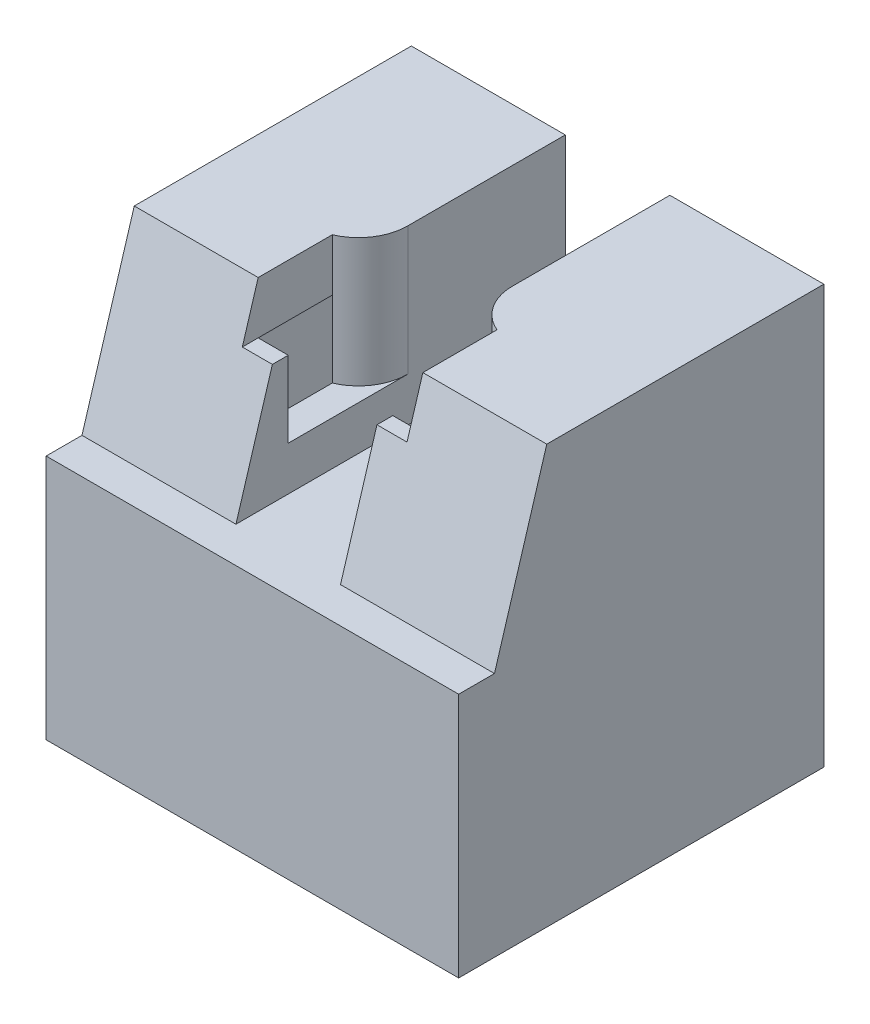
SolidWorks part; units mm, degrees
ref_plane "Front Plane" through (0, 0, 0) normal (0, 0, 1) x (1, 0, 0)
ref_plane "Top Plane" through (0, 0, 0) normal (0, 1, 0) x (1, 0, 0)
ref_plane "Right Plane" through (0, 0, 0) normal (1, 0, 0) x (0, 0, -1)
sketch "Sketch2" plane through (0, 0, 0) normal (0, 1, 0) x (1, 0, 0)
  line L1 (-9.35, 10) -> (9.35, 10)
  line L2 (-9.35, 10) -> (-9.35, -10)
  line L3 (-9.35, -10) -> (9.35, -10)
  line L4 (9.35, 10) -> (9.35, -10)
  point P4 (0, 10)
  point P6 (-9.35, 0)
  dimension "D1" = 18.7
  dimension "D2" = 20
extrude "Boss-Extrude1" add sketch "Sketch2" along normal blind 25.4
sketch "Sketch3" plane through (0, 0, -10) normal (0, 0, -1) x (-1, 0, 0)
  line L0 (-9.35, 25.4) -> (9.35, 25.4) construction
  line L1 (-3.175, 25.4) -> (3.175, 25.4)
  line L2 (-3.175, 25.4) -> (-3.175, 18.1)
  line L3 (-3.175, 18.1) -> (3.175, 18.1)
  line L4 (3.175, 25.4) -> (3.175, 18.1)
  line L5 (-9.35, 22.225) -> (9.35, 22.225) construction
  line L6 (-9.35, 25.4) -> (-9.35, 0) construction
  line L7 (9.35, 25.4) -> (9.35, 0) construction
  line L9 (-3.175, 18.1) -> (3.175, 18.1)
  line L10 (-3.175, 18.1) -> (-3.175, 14.925)
  line L11 (-3.175, 14.925) -> (3.175, 14.925)
  line L12 (3.175, 18.1) -> (3.175, 14.925)
  point P6 (0, 18.1)
  point P9 (6.0716, 19.725)
  line M12 (9.35, 25.4) -> (-9.35, 25.4)
  dimension "D1" = 6.35
  dimension "D2" = 3.175
  dimension "D3" = 2.5
  dimension "D4" = 1.625
  dimension "D5" = 3.175
extrude "Cut-Extrude1" cut sketch "Sketch3" against normal through all contours L12 L3 L10 L11 | L5 L2 L3 L4 | L2 L5 L4 M12 region at (0, 23.8125, -10) region at (0, 20.1625, -10) region at (0, 16.5125, -10)
sketch "Sketch5" plane through (0, 0, -10) normal (0, 0, -1) x (-1, 0, 0)
  line L0 (9.35, 25.4) -> (9.35, 0) construction
  line L1 (-9.35, 25.4) -> (-12.525, 25.4)
  line L2 (-9.35, 25.4) -> (-9.35, 0)
  line L3 (-9.35, 0) -> (-12.525, 0)
  line L4 (-12.525, 25.4) -> (-12.525, 0)
  line L5 (9.35, 25.4) -> (12.525, 25.4)
  line L6 (9.35, 25.4) -> (9.35, 0)
  line L7 (9.35, 0) -> (12.525, 0)
  line L8 (12.525, 25.4) -> (12.525, 0)
  line L9 (-9.35, 0) -> (9.35, 0) construction
  dimension "D1" = 3.175
extrude "Boss-Extrude2" add sketch "Sketch5" against normal up to surface (20 mm away) up to face at (0, 16.4312, 10)
sketch "Sketch6" plane through (0, 0, -10) normal (0, 0, -1) x (-1, 0, 0)
  line L0 (-12.525, 0) -> (12.525, 0) construction
  line L1 (-9.35, 22.225) -> (-5, 22.225)
  line L2 (-9.35, 22.225) -> (-9.35, 0)
  line L3 (-9.35, 0) -> (-5, 0)
  line L4 (-5, 22.225) -> (-5, 0)
  line L5 (-3.175, 14.925) -> (3.175, 14.925) construction
  line L6 (-5, 10.125) -> (5, 10.125)
  line L7 (-5, 10.125) -> (-5, 0)
  line L8 (-5, 0) -> (5, 0)
  line L9 (5, 10.125) -> (5, 0)
  line L10 (9.35, 0) -> (5, 0)
  line L11 (9.35, 0) -> (9.35, 22.225)
  line L12 (9.35, 22.225) -> (5, 22.225)
  line L13 (5, 0) -> (5, 22.225)
  line L14 (-12.525, 25.4) -> (-3.175, 25.4) construction
  point P12 (0, 10.125)
  point P15 (0, 14.925)
  line M18 (-12.525, 0) -> (12.525, 0)
  dimension "D1" = 10
  dimension "D2" = 18.7
  dimension "D3" = 3.175
  dimension "D4" = 12.1
extrude "Cut-Extrude2" cut sketch "Sketch6" against normal blind 16.825 contours L13 L9 L11 L12 M18 | L9 L6 L4 M18 | L4 L1 L2 M18 region at (7.175, 11.1125, -10) region at (0, 5.0625, -10) region at (-7.175, 11.1125, -10)
sketch "Sketch7" plane through (5, 0, 0) normal (1, 0, 0) x (0, 0, -1)
  line L0 (-6.825, 22.225) -> (-6.825, 10.125) construction
  line L1 (-6.325, 21.475) -> (-3.325, 21.475)
  line L2 (-6.325, 21.475) -> (-6.325, 17.975)
  line L3 (-6.325, 17.975) -> (-3.325, 17.975)
  line L4 (-3.325, 21.475) -> (-3.325, 17.975)
  line L5 (-6.825, 22.225) -> (10, 22.225) construction
  point P6 (-4.825, 17.975)
  point P7 (-6.325, 19.725)
  dimension "D1" = 3
  dimension "D2" = 2
  dimension "D3" = 2.5
  dimension "D4" = 3.5
extrude "Cut-Extrude3" cut sketch "Sketch7" against normal up to surface (10 mm away) up to face at (-5, 16.175, -1.5875)
sketch "Sketch8" plane through (0, 0, -10) normal (0, 0, -1) x (-1, 0, 0)
  line L0 (9.35, 0) -> (12.525, 0) construction
  line L1 (-11, 10.125) -> (11, 10.125)
  line L2 (-11, 10.125) -> (-11, 0)
  line L3 (-11, 0) -> (11, 0)
  line L4 (11, 10.125) -> (11, 0)
  line L5 (-5, 10.125) -> (5, 10.125) construction
  point P9 (0, 10.125)
  dimension "D1" = 22
extrude "Cut-Extrude4" cut sketch "Sketch8" against normal blind 19
sketch "Sketch9" plane through (12.525, 0, 0) normal (1, 0, 0) x (0, 0, -1)
  line L0 (-10, 0) -> (-10, 25.4) construction
  line L1 (-10, 14.925) -> (-12.175, 14.925)
  line L2 (-10, 14.925) -> (-10, 0)
  line L3 (-10, 0) -> (-12.175, 0)
  line L4 (-12.175, 14.925) -> (-12.175, 0)
  line L5 (-10, 0) -> (10, 0) construction
  dimension "D1" = 3.175
extrude "Boss-Extrude3" add sketch "Sketch9" against normal up to surface (25.05 mm away) up to face at (-12.525, 12.7, 0)
ref_plane "Plane1" through (0, 0, 2.325) normal (0, 0, -1) x (-1, 0, 0)
sketch "Sketch10" plane through (0, 0, 2.325) normal (0, 0, -1) x (-1, 0, 0)
  line L0 (-5, 22.225) -> (-5, 10.125) construction
  line L1 (-5, 25.4) -> (-3.175, 25.4)
  line L2 (-5, 25.4) -> (-5, 17.6)
  line L3 (-5, 17.6) -> (-3.175, 17.6)
  line L4 (-3.175, 25.4) -> (-3.175, 17.6)
  line L5 (3.175, 25.4) -> (3.175, 14.925) construction
  line L6 (3.175, 25.4) -> (5, 25.4)
  line L7 (3.175, 25.4) -> (3.175, 17.6)
  line L8 (3.175, 17.6) -> (5, 17.6)
  line L9 (5, 25.4) -> (5, 17.6)
  line L10 (5, 10.125) -> (5, 22.225) construction
  line L11 (-12.525, 25.4) -> (-3.175, 25.4) construction
  line L12 (5, 10.125) -> (5, 22.225) construction
  line L13 (-3.175, 25.4) -> (-3.175, 14.925) construction
  line L14 (-3.175, 14.925) -> (3.175, 14.925) construction
  dimension "D1" = 2.675
extrude "Cut-Extrude5" cut sketch "Sketch10" against normal up to surface (4.5 mm away) up to face at (-7.175, 16.175, 6.825)
sketch "Sketch11" plane through (12.525, 0, 0) normal (1, 0, 0) x (0, 0, -1)
  line L0 (-6.825, 25.4) -> (-10, 14.925)
  line L2 (-10, 14.925) -> (-10, 25.4) construction
  line L3 (-10, 14.925) -> (-10, 25.4)
  line L4 (-10, 25.4) -> (-6.825, 25.4)
  line L7 (-10, 25.4) -> (10, 25.4) construction
  line L8 (-10, 14.925) -> (-12.175, 14.925) construction
  point P2 (0, 0)
  point P3 (-3.0332, 25.4)
  point P6 (1.9842, 25.4)
  point P9 (-5.5322, 25.4)
  point P14 (-6.825, 21.3585)
  point P17 (-6.825, 17.7451)
  point P20 (0, 0)
  line M4 (-10, 25.4) -> (-10, 14.925)
  line M9 (10, 25.4) -> (-10, 25.4)
extrude "Cut-Extrude6" cut sketch "Sketch11" against normal through all contours L0 M9 M4 region at (12.525, 21.9083, 8.9417)
sketch "Sketch15" plane through (-5, 0, 0) normal (1, 0, 0) x (0, 0, -1)
  line L1 (-6.825, 25.4) -> (-7.7874, 25.4)
  line L2 (-6.825, 25.4) -> (-6.825, 22.225)
  line L3 (-6.825, 22.225) -> (-7.7874, 22.225)
  line L4 (-7.7874, 25.4) -> (-7.7874, 22.225)
  line L8 (-6.825, 22.225) -> (-2.325, 22.225) construction
  line L9 (-6.825, 25.4) -> (-10, 14.925) construction
  point P7 (-9.1668, 25.4)
  point P8 (-7.7874, 22.225)
  point P9 (0, 0)
  point P12 (0, 0)
  point P13 (0, 0)
extrude "Cut-Extrude8" cut sketch "Sketch15" along normal up to surface (10 mm away) up to face at (5, 23.8125, 4.575)
fillet "Fillet1" radius 3 2 edges at (3.175, 21.5, 2.325) (-3.175, 21.5, 2.325)
